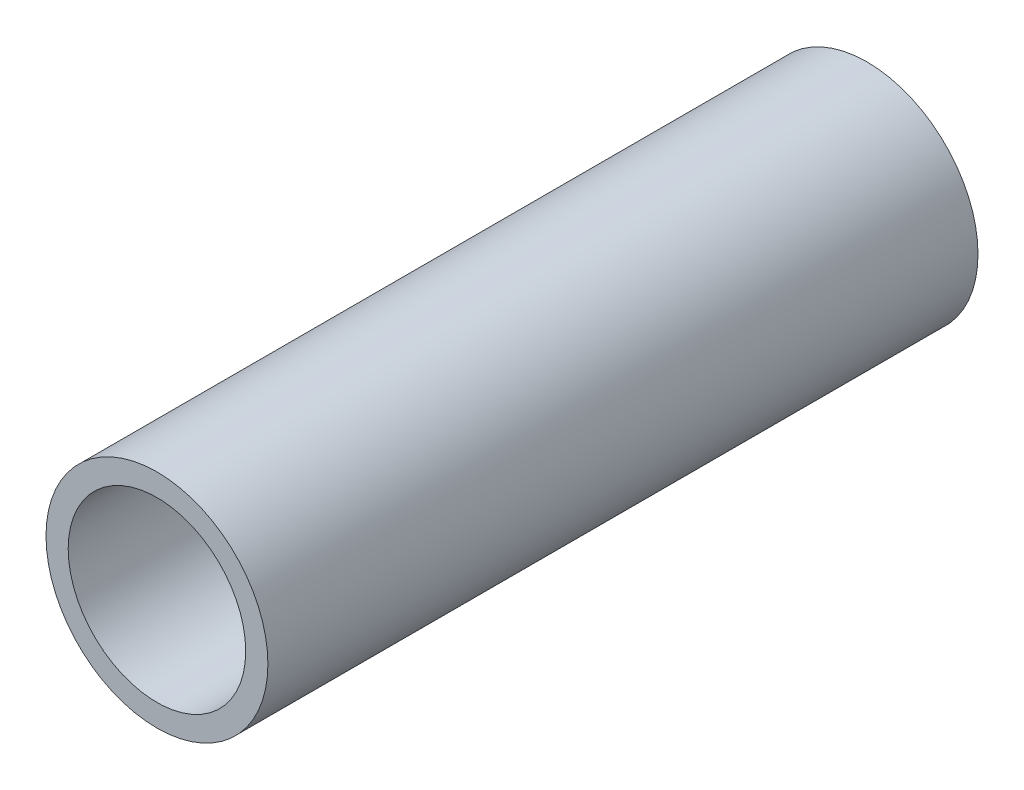
SolidWorks part; units mm, degrees
material "Nylon 101"
ref_plane "Front Plane" through (0, 0, 0) normal (0, 0, 1) x (1, 0, 0)
ref_plane "Top Plane" through (0, 0, 0) normal (0, 1, 0) x (1, 0, 0)
ref_plane "Right Plane" through (0, 0, 0) normal (1, 0, 0) x (0, 0, -1)
sketch "Sketch1" plane through (0, 0, 0) normal (0, 0, 1) x (1, 0, 0)
  circle A0 centre (0, 0) radius 6.35
  circle A1 centre (0, 0) radius 7.9375
  dimension "D1" = 12.7
  dimension "D2" = 15.875
extrude "Boss-Extrude1" add sketch "Sketch1" along normal mid plane 50.8
